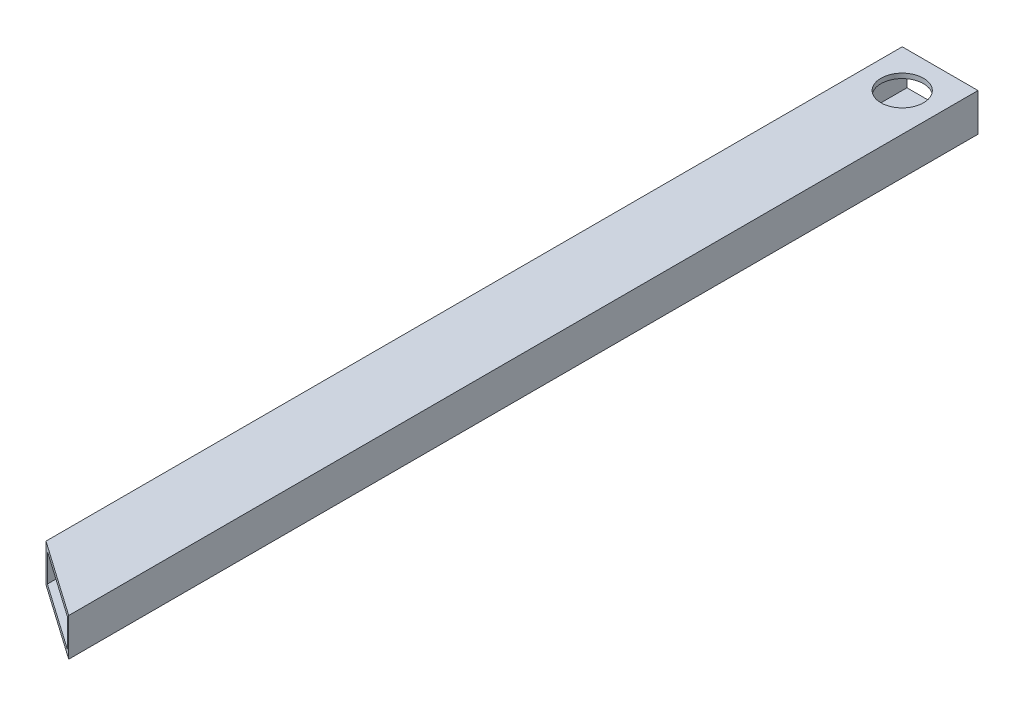
SolidWorks part; units mm, degrees
ref_plane "Front Plane" through (0, 0, 0) normal (0, 0, 1) x (1, 0, 0)
ref_plane "Top Plane" through (0, 0, 0) normal (0, 1, 0) x (1, 0, 0)
ref_plane "Right Plane" through (0, 0, 0) normal (1, 0, 0) x (0, 0, -1)
sketch "Sketch1" plane through (0, 0, 0) normal (0, 0, 1) x (1, 0, 0)
  line L1 (0, 0) -> (50.8, 0)
  line L2 (0, 0) -> (0, 25.4)
  line L3 (0, 25.4) -> (50.8, 25.4)
  line L4 (50.8, 0) -> (50.8, 25.4)
extrude "Boss-Extrude1" add sketch "Sketch1" along normal blind 609.6
sketch "Sketch2" plane through (0, 0, 0) normal (0, 0, -1) x (-1, 0, 0)
  line L1 (-3.175, 3.175) -> (-47.625, 3.175)
  line L2 (-3.175, 3.175) -> (-3.175, 22.225)
  line L3 (-3.175, 22.225) -> (-47.625, 22.225)
  line L4 (-47.625, 3.175) -> (-47.625, 22.225)
extrude "Cut-Extrude1" cut sketch "Sketch2" against normal blind 609.6
sketch "Sketch6" plane through (0, 25.4, 0) normal (0, 1, 0) x (1, 0, 0)
  line L0 (25.4, 0) -> (25.4, -25.4) construction
  line L1 (50.8, 0) -> (0, 0) construction
  circle A0 centre (25.4, -25.4) radius 14.2875
extrude "Cut-Extrude5" cut sketch "Sketch6" against normal blind 3.175
sketch "Sketch7" plane through (0, 0, 0) normal (0, -1, 0) x (1, 0, 0)
  line L0 (50.8, 609.6) -> (0, 574.0295)
  line L1 (0, 609.6) -> (0, 0) construction
  line L2 (0, 574.0295) -> (0, 609.6)
  line L3 (0, 609.6) -> (50.8, 609.6)
  dimension "D1" = 35
extrude "Cut-Extrude6" cut sketch "Sketch7" against normal blind 25.4
